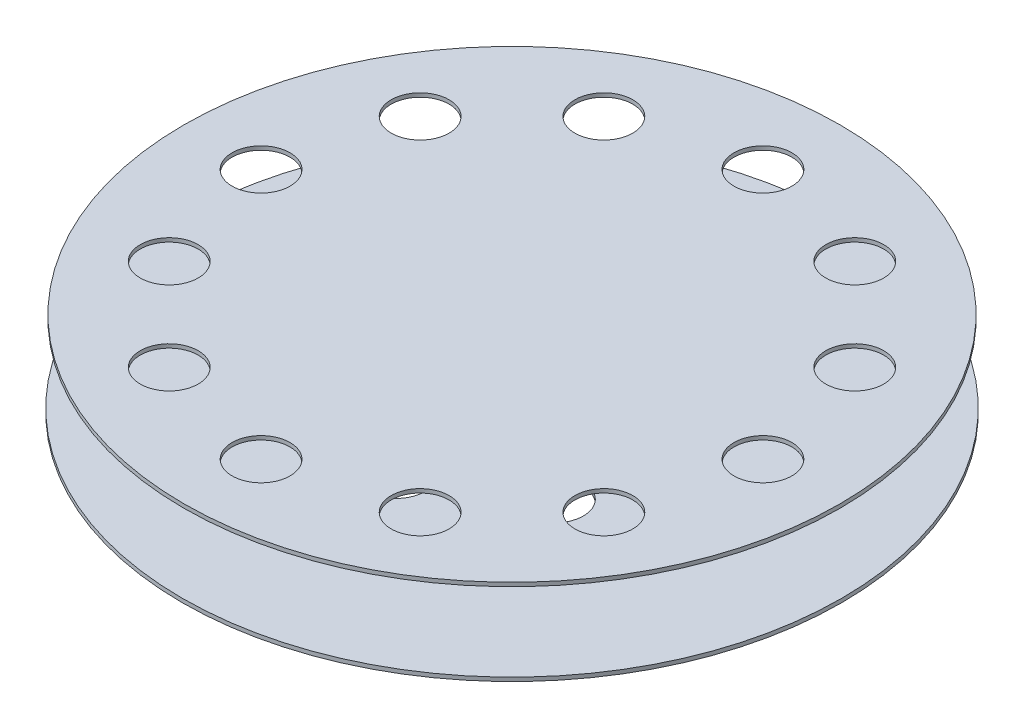
SolidWorks part; units mm, degrees
ref_plane "Front Plane" through (0, 0, 0) normal (0, 0, 1) x (1, 0, 0)
ref_plane "Top Plane" through (0, 0, 0) normal (0, 1, 0) x (1, 0, 0)
ref_plane "Right Plane" through (0, 0, 0) normal (1, 0, 0) x (0, 0, -1)
sketch "Sketch1" plane through (0, 0, 0) normal (0, 0, 1) x (1, 0, 0)
  line L0 (0, 0) -> (0, 52.2611) construction
  line L1 (0, 62) -> (-84.9998, 62)
  line L2 (-84.9998, 62) -> (-84.9998, 61)
  line L3 (-84.9998, 61) -> (-5, 61)
  line L4 (-5, 61) -> (-5, 41)
  line L5 (-5, 41) -> (-85.4031, 41)
  line L6 (-85.4031, 41) -> (-85.4031, 40)
  line L7 (-85.4031, 40) -> (-5, 40)
  line L8 (-5, 40) -> (-5, 0)
  line L9 (-5, 0) -> (0, 0)
  line L10 (0, 0) -> (0, 62)
  line L11 (-5, 41) -> (-5, 40) construction
  dimension "D1" = 84.9998
  dimension "D2" = 1
  dimension "D3" = 20
  dimension "D4" = 5
  dimension "D5" = 40
ref_axis "Axis1" through (0, 54.8742, 0) along (0, -1, 0)
revolve "Revolve1" add sketch "Sketch1" angle 360 about axis through (0, 54.8742, 0) along (0, -1, 0)
sketch "Sketch2" plane through (0, 62, 0) normal (0, 1, 0) x (1, 0, 0)
  line L0 (0, 0) -> (0, 65) construction
  circle A0 centre (0, 65) radius 7.5
  dimension "D1" = 15
  dimension "D2" = 65
extrude "Cut-Extrude1" cut sketch "Sketch2" against normal blind 2
pattern_circular "CirPattern1" count 12 over 360 about axis through (0, 54.8742, 0) along (0, -1, 0) of "Cut-Extrude1"
sketch "Sketch3" plane through (0, 40, 0) normal (0, -1, 0) x (1, 0, 0)
  line L0 (0, 0) -> (0, 30) construction
  circle A0 centre (0, 30) radius 7.5
  dimension "D2" = 15
  dimension "D1" = 30
extrude "Cut-Extrude2" cut sketch "Sketch3" against normal blind 2
pattern_circular "CirPattern2" count 6 over 360 about axis through (0, 54.8742, 0) along (0, -1, 0) of "Cut-Extrude2"
